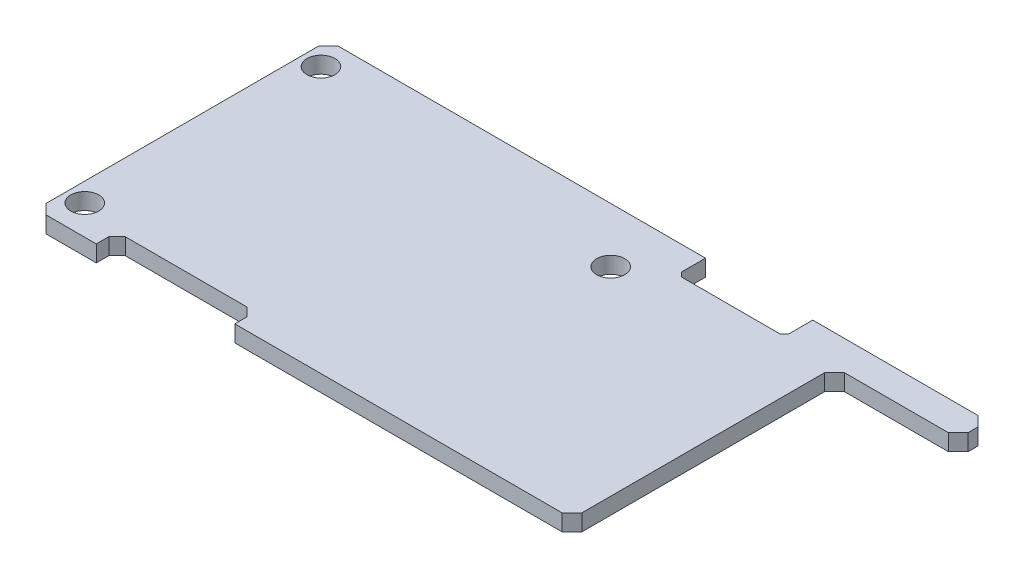
SolidWorks part; units mm, degrees
ref_plane "前视基准面" through (0, 0, 0) normal (0, 0, 1) x (1, 0, 0)
ref_plane "上视基准面" through (0, 0, 0) normal (0, 1, 0) x (1, 0, 0)
ref_plane "右视基准面" through (0, 0, 0) normal (1, 0, 0) x (0, 0, -1)
other "Configuration Table"
sketch "草图1" plane through (0, 0, 0) normal (0, 1, 0) x (1, 0, 0)
  line L1 (0, 0) -> (80, 0)
  line L2 (0, 0) -> (0, 35.45)
  line L3 (0, 35.45) -> (80, 35.45)
  line L4 (80, 0) -> (80, 35.45)
  dimension "D1" = 80
  dimension "D2" = 35.45
extrude "凸台-拉伸1" add sketch "草图1" along normal blind 2
sketch "草图2" plane through (0, 2, 0) normal (0, 1, 0) x (1, 0, 0)
  line L0 (65, 0) -> (65, 31.85)
  line L1 (65, 31.85) -> (80, 31.85)
  line L4 (0, 35.45) -> (0, 0)
  line L5 (0, 0) -> (80, 0)
  line L6 (80, 0) -> (80, 35.45)
  line L7 (80, 35.45) -> (0, 35.45)
  line L8 (0, 35.45) -> (0, 0)
  line L9 (0, 0) -> (80, 0)
  line L10 (80, 0) -> (80, 35.45)
  line L11 (80, 35.45) -> (0, 35.45)
  line M8 (0, 0) -> (80, 0)
  line M9 (80, 0) -> (80, 35.45)
  dimension "D1" = 0
  dimension "D2" = 3.6
  dimension "D3" = 15
extrude "切除-拉伸1" cut sketch "草图2" against normal through all contours L1 L0 M8 M9 region at (72.5, 2, -15.925)
sketch "草图3" plane through (0, 2, 0) normal (0, 1, 0) x (1, 0, 0)
  line L0 (2.3, 0) -> (2.3, 35.45) construction
  line L1 (0, 0) -> (65, 0) construction
  line L2 (80, 35.45) -> (0, 35.45) construction
  line L3 (0, 35.45) -> (0, 0) construction
  circle A0 centre (2.3, 3.6) radius 1.7
  circle A1 centre (2.3, 32.25) radius 1.7
  circle A2 centre (40.8906, 28.8025) radius 1.7
  dimension "D2" = 3.4
  dimension "D3" = 3.4
  dimension "D6" = 3.4
  dimension "D1" = 2.3
  dimension "D4" = 3.6
  dimension "D5" = 3.2
extrude "切除-拉伸2" cut sketch "草图3" against normal through all
sketch "草图4" plane through (0, 2, 0) normal (0, 1, 0) x (1, 0, 0)
  line L10 (24.1, -2.0794) -> (24.1, 2.5106)
  line L11 (24.1, 2.5106) -> (7.3, 2.5142)
  line L12 (7.3, 2.5142) -> (7.3, -2.0794)
  line L13 (7.3, -2.0794) -> (24.1, -2.0794)
  line L14 (58.7566, 37.5285) -> (45.7452, 37.5285)
  line L15 (45.7452, 37.5285) -> (45.7452, 32.5659)
  line L16 (45.7452, 32.5659) -> (46.2976, 32.0135)
  line L17 (46.2976, 32.0135) -> (58.1977, 32.01)
  line L18 (58.1977, 32.01) -> (58.7566, 32.5659)
  line L19 (58.7566, 32.5659) -> (58.7566, 37.5285)
extrude "切除-拉伸3" cut sketch "草图4" against normal through all
chamfer "倒角1" distance 1 angle 45 2 edges at (24.1, 1, -2.5106) (7.3, 1, -2.5142) first distance on face at (15.7, 1, -2.5124)
chamfer "倒角2" distance 1.2 angle 45 6 edges at (65, 1, -31.85) (65, 1, 0) (80, 1, -31.85) (80, 1, -35.45) (0, 1, -35.45) (0, 1, 0)
